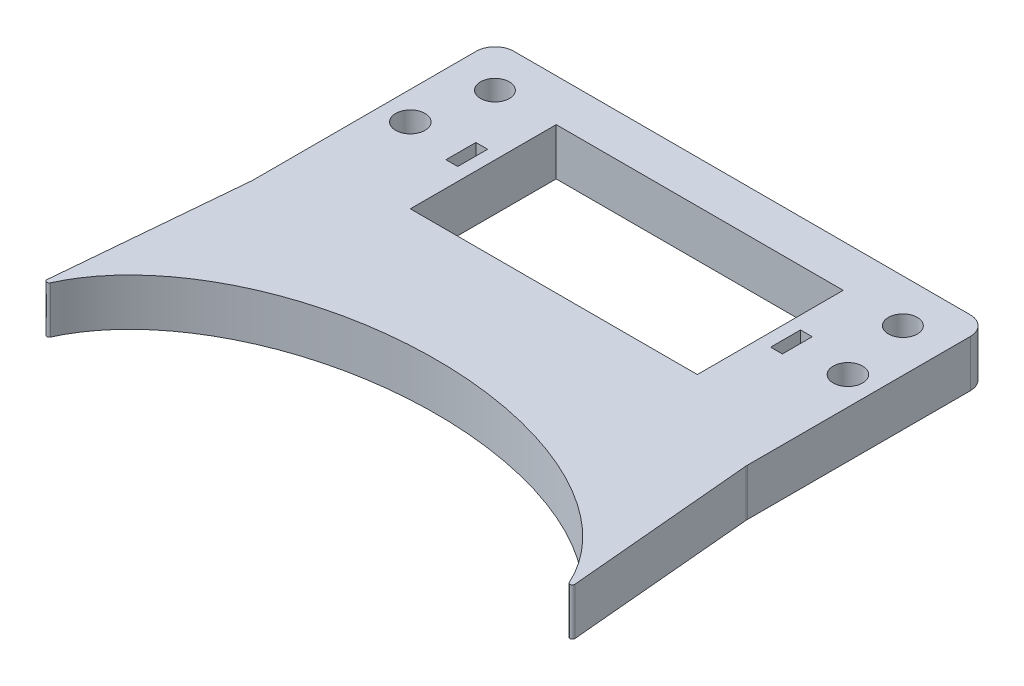
SolidWorks part; units mm, degrees
ref_plane "Front Plane" through (0, 0, 0) normal (0, 0, 1) x (1, 0, 0)
ref_plane "Top Plane" through (0, 0, 0) normal (0, 1, 0) x (1, 0, 0)
ref_plane "Right Plane" through (0, 0, 0) normal (1, 0, 0) x (0, 0, -1)
sketch "Sketch1" plane through (0, 0, 0) normal (0, 1, 0) x (1, 0, 0)
  line L1 (-52.5, -32.5) -> (52.5, -32.5)
  line L2 (-52.5, -32.5) -> (-52.5, 32.5)
  line L3 (-52.5, 32.5) -> (52.5, 32.5)
  line L4 (52.5, -32.5) -> (52.5, 32.5)
  line L5 (0, 32.5) -> (0, -32.5) construction
  line L6 (-52.5, 0) -> (52.5, 0) construction
  point P0 (0, 0)
  dimension "D1" = 105
  dimension "D2" = 65
extrude "Boss-Extrude1" add sketch "Sketch1" along normal blind 10
sketch "Sketch2" plane through (0, 10, 0) normal (0, 1, 0) x (1, 0, 0)
  line L6 (-30.5, 23.5) -> (30.5, 23.5)
  line L7 (-30.5, 23.5) -> (-30.5, -7.5)
  line L8 (-30.5, -7.5) -> (30.5, -7.5)
  line L9 (30.5, 23.5) -> (30.5, -7.5)
  line L10 (0, -7.5) -> (0, 23.5) construction
  line L11 (-30.5, 8) -> (30.5, 8) construction
  line L12 (0, 0) -> (0, -7.5) construction
  line L14 (-52.5, -32.5) -> (52.5, -32.5) construction
  point P0 (0, 8)
  dimension "D1" = 31
  dimension "D2" = 61
  dimension "D3" = 25
extrude "Cut-Extrude1" cut sketch "Sketch2" against normal through all
sketch "Sketch4" plane through (0, 10, 0) normal (0, 1, 0) x (1, 0, 0)
  line L2 (-46.5, 8.5) -> (-34.5, 8.5) construction
  line L3 (30.5, 23.5) -> (-30.5, 23.5) construction
  line L4 (-33.25, 11.675) -> (-35.75, 11.675)
  line L5 (-33.25, 11.675) -> (-33.25, 5.325)
  line L6 (-33.25, 5.325) -> (-35.75, 5.325)
  line L7 (-35.75, 11.675) -> (-35.75, 5.325)
  line L8 (-34.5, 5.325) -> (-34.5, 11.675) construction
  line L9 (-33.25, 8.5) -> (-35.75, 8.5) construction
  line L10 (-30.5, 23.5) -> (-30.5, -7.5) construction
  circle A0 centre (-46.5, 8.5) radius 3.125
  dimension "D1" = 6.25
  dimension "D2" = 15
  dimension "D3" = 16
  dimension "D4" = 2.5
  dimension "D5" = 6.35
  dimension "D6" = 2.75
extrude "Cut-Extrude3" cut sketch "Sketch4" against normal through all
sketch "Sketch5" plane through (0, 0, 0) normal (0, 1, 0) x (1, 0, 0)
  line L0 (0, 0) -> (0, -70) construction
  line L1 (-52.5, -32.5) -> (52.5, -32.5) construction
  line L2 (-52.5, -19.0391) -> (-56.4081, -62.7266)
  line L3 (-52.5, 32.5) -> (-52.5, -32.5) construction
  line L4 (-52.5, -19.0391) -> (0, -32.5)
  ellipse E0 centre (0, -70) end of major axis (-57.5, -70) minor radius 37.5
  point P14 (-60.0581, -51.0042)
  dimension "D1" = 115
  dimension "D2" = 70
extrude "Boss-Extrude2" add sketch "Sketch5" along normal up to surface (10 mm away) contours E0 L4 L2 region at (-39.0021, 0, 34.1841) up to face at (-46.5, 10, -5.375)
sketch "Sketch6" plane through (0, 10, 0) normal (0, 1, 0) x (1, 0, 0)
  circle A0 centre (-43.3477, 23.3308) radius 3.075
  point P2 (-44.1085, 18.5417)
  point P3 (-43.3477, 23.3308)
  dimension "D1" = 6.15
extrude "Cut-Extrude4" cut sketch "Sketch6" against normal through all
mirror "Mirror1" about plane through (0, 0, 0) normal (1, 0, 0) of "Cut-Extrude4", "Boss-Extrude2", "Cut-Extrude3"
fillet "Fillet1" radius 4 4 edges at (-52.5, 5, 19.0391) (52.5, 5, 19.0391) (52.5, 5, -32.5) (-52.5, 5, -32.5)
fillet "Fillet2" radius 0.5 2 edges at (56.4081, 5, 62.7266) (-56.4081, 5, 62.7266)
